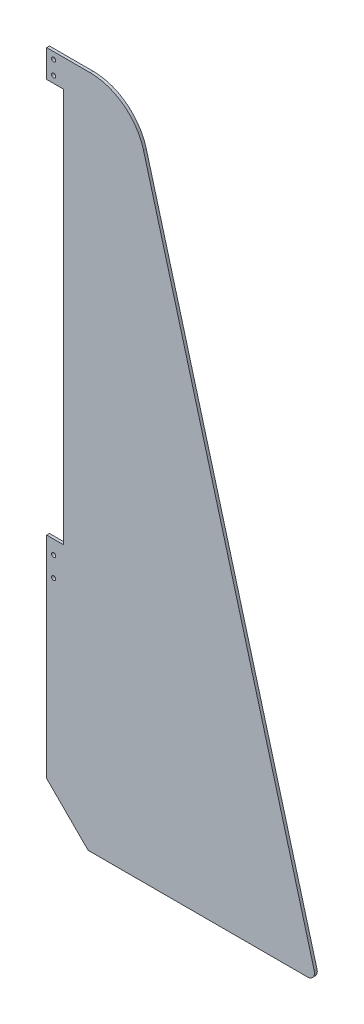
SolidWorks part; units mm, degrees
ref_plane "Front Plane" through (0, 0, 0) normal (0, 0, 1) x (1, 0, 0)
ref_plane "Top Plane" through (0, 0, 0) normal (0, 1, 0) x (1, 0, 0)
ref_plane "Right Plane" through (0, 0, 0) normal (1, 0, 0) x (0, 0, -1)
sketch "Sketch2" plane through (0, 0, 0) normal (0, 0, 1) x (1, 0, 0)
  line L0 (0, -44.1522) -> (0, 108.6729)
  line L1 (10, 414.5527) -> (-66, 414.5527) construction
  line L2 (0, 414.5527) -> (31.5712, 414.5527)
  line L3 (70.1584, 385.0898) -> (193.839, -67.8351)
  line L4 (189.0157, -74.1522) -> (30, -74.1522)
  line L5 (0, 108.6729) -> (12, 108.6729)
  line L6 (12, 108.6729) -> (12, 394.5527) construction
  line L7 (12, 108.6729) -> (12, 394.5527)
  line L8 (12, 394.5527) -> (0, 394.5527)
  line L9 (-66, 394.5527) -> (10, 394.5527) construction
  line L10 (0, 414.5527) -> (0, 394.5527)
  line L11 (30, -74.1522) -> (0, -44.1522)
  arc A0 (31.5712, 414.5527) -> (70.1584, 385.0898) centre (31.5712, 374.5527) cw
  arc A1 (189.0157, -74.1522) -> (193.839, -67.8351) centre (189.0157, -69.1522) ccw
  point P8 (0, -74.1522)
  dimension "D1" = 40
  dimension "D2" = 5
sketch "Sketch3" plane through (0, 0, 0) normal (0, 1, 0) x (1, 0, 0)
  line L0 (0, 0) -> (0, 2.7635) construction
ref_plane "Plane1" through (0, 0, 0) normal (0, 0, -1) x (-1, 0, 0)
extrude "Boss-Extrude1" add sketch "Sketch2" along normal blind 2 contours L2 A0 L3 A1 L4 L11 L0 L5 L7 L8 L10
sketch "Sketch6" plane through (0, 0, 2) normal (0, 0, 1) x (1, 0, 0)
  line L0 (4.9868, 98.6729) -> (4.9868, 130.4408) construction
  line L1 (-66, 394.5527) -> (10, 394.5527) construction
  line L2 (0, 414.5527) -> (31.5712, 414.5527) construction
  circle A0 centre (4.9868, 98.6729) radius 1.5
  circle A1 centre (4.9868, 84.1729) radius 1.5
  circle A2 centre (4.9868, 399.5527) radius 1.5
  circle A3 centre (4.9868, 409.5527) radius 1.5
  dimension "D1" = 5
  dimension "D2" = 5
extrude "Cut-Extrude2" cut sketch "Sketch6" against normal through all
